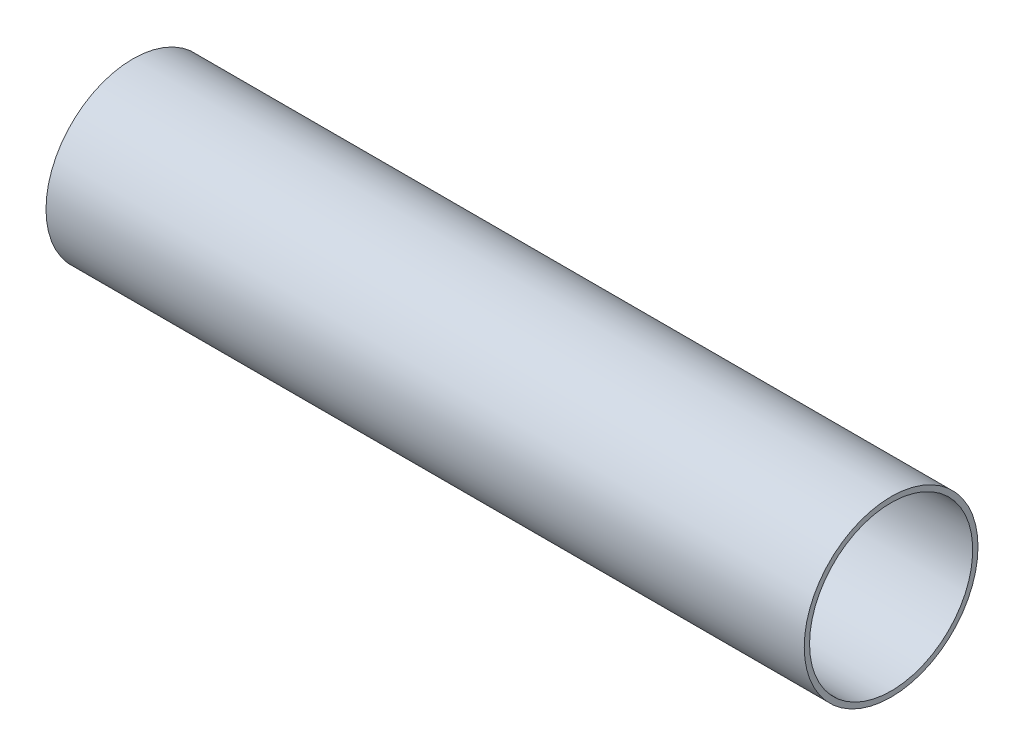
SolidWorks part; units mm, degrees
material "Copper"
ref_plane "Front" through (0, 0, 0) normal (0, 0, 1) x (1, 0, 0)
ref_plane "Top" through (0, 0, 0) normal (0, 1, 0) x (1, 0, 0)
ref_plane "Right" through (0, 0, 0) normal (1, 0, 0) x (0, 0, -1)
sketch "Sketch1" plane through (0, 0, 0) normal (1, 0, 0) x (0, 0, -1)
  circle A0 centre (0, 0) radius 17.4625
  circle A1 centre (0, 0) radius 16.3957
  point P4 (17.4625, 0)
  point P5 (16.3957, 0)
  dimension "OD" = 34.925
  dimension "ID" = 32.7914
  dimension "Wall" = 1.0668
extrude "Extrude1" add sketch "Sketch1" along normal mid plane 152.4
sketch "Sketch2" plane through (0, 0, 0) normal (0, 0, 1) x (1, 0, 0)
  line L0 (-76.2, 0) -> (76.2, 0) construction
  line L1 (-76.2, 17.4625) -> (-76.2, -17.4625) construction
